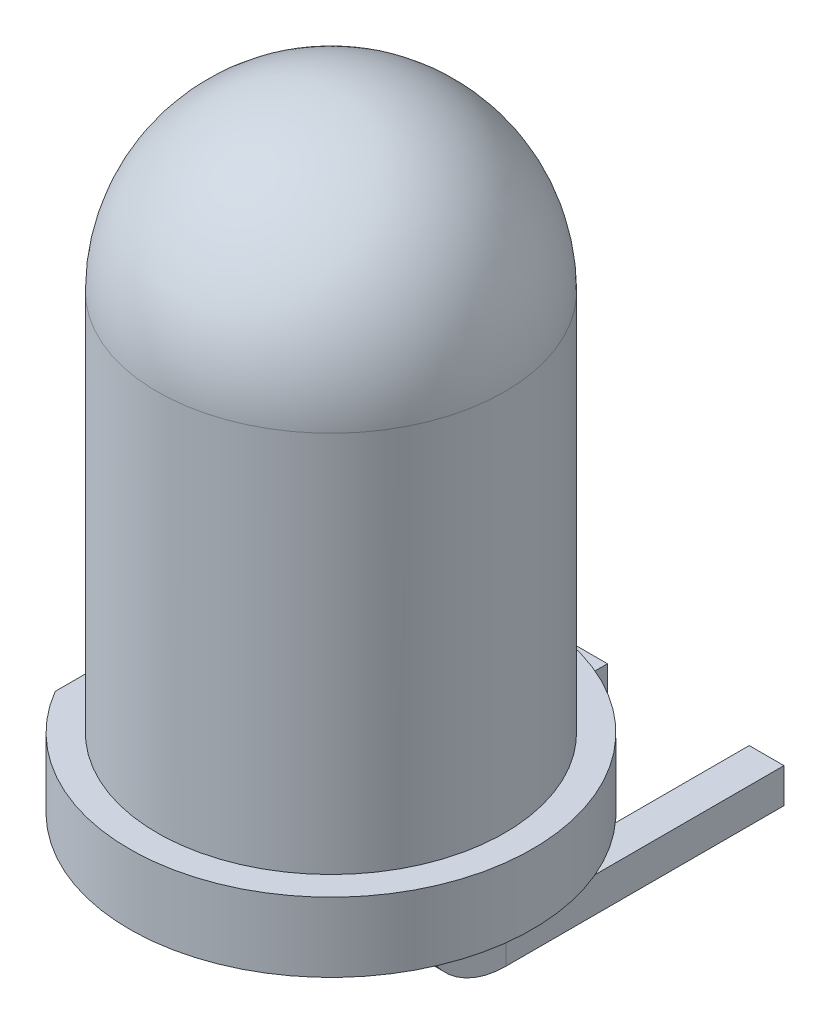
SolidWorks part; units mm, degrees
ref_plane "Front Plane" through (0, 0, 0) normal (0, 0, 1) x (1, 0, 0)
ref_plane "Top Plane" through (0, 0, 0) normal (0, 1, 0) x (1, 0, 0)
ref_plane "Right Plane" through (0, 0, 0) normal (1, 0, 0) x (0, 0, -1)
sketch "Sketch1" plane through (0, 0, 0) normal (0, 0, -1) x (1, 0, 0)
  line L0 (0, 0) -> (0, -9)
  line L1 (2.5, -6.5) -> (2.5, -1)
  line L2 (2.9, 0) -> (0, 0)
  line L3 (2.5, -1) -> (2.9, -1)
  line L4 (2.9, -1) -> (2.9, 0)
  arc A0 (2.5, -6.5) -> (0, -9) centre (0, -6.5) cw
  dimension "D1" = 2.5
  dimension "D2" = 2.9
  dimension "D3" = 1
  dimension "D4" = 9
revolve "Revolve1" add sketch "Sketch1" angle 360 about L0
sketch "Sketch2" plane through (0, 0, 0) normal (0, -1, 0) x (-1, 0, 0)
  line L1 (2.9, 1.4697) -> (2.5, 1.4697)
  line L2 (2.9, 1.4697) -> (2.9, -1.4697)
  line L3 (2.9, -1.4697) -> (2.5, -1.4697)
  line L4 (2.5, 1.4697) -> (2.5, -1.4697)
  circle A0 centre (0, 0) radius 2.5 construction
  circle A1 centre (0, 0) radius 2.9 construction
extrude "Cut-Extrude1" cut sketch "Sketch2" against normal through all
sketch "Sketch3" plane through (0, 0, 0) normal (0, -1, 0) x (-1, 0, 0)
  line L0 (0, 1.7562) -> (0, 0) construction
  line L1 (0, 0) -> (1.27, 0) construction
  line L2 (-1.02, 0.25) -> (-1.02, -0.25)
  line L3 (1.02, 0.25) -> (1.52, 0.25)
  line L4 (1.02, 0.25) -> (1.02, -0.25)
  line L5 (1.02, -0.25) -> (1.52, -0.25)
  line L6 (1.52, 0.25) -> (1.52, -0.25)
  line L7 (1.02, 0.25) -> (1.52, -0.25) construction
  line L8 (1.02, -0.25) -> (1.52, 0.25) construction
  line L9 (-1.02, -0.25) -> (-1.52, -0.25)
  line L10 (-1.52, 0.25) -> (-1.52, -0.25)
  line L11 (-1.02, 0.25) -> (-1.52, 0.25)
  dimension "D1" = 0.5
  dimension "D2" = 1.27
ref_plane "Plane1" through (-1.27, 0, 0) normal (1, 0, 0) x (0, 0, -1)
sketch "Sketch4" plane through (-1.27, 0, 0) normal (1, 0, 0) x (0, 0, -1)
  line L0 (0, 0) -> (0, -0.4)
  line L1 (1, -1.4) -> (5, -1.4)
  arc A0 (0, -0.4) -> (1, -1.4) centre (1, -0.4) ccw
  dimension "D3" = 5
  dimension "D2" = 1
  dimension "D1" = 0.4
sweep "Sweep1" add profiles "Sketch3" path "Sketch4"
